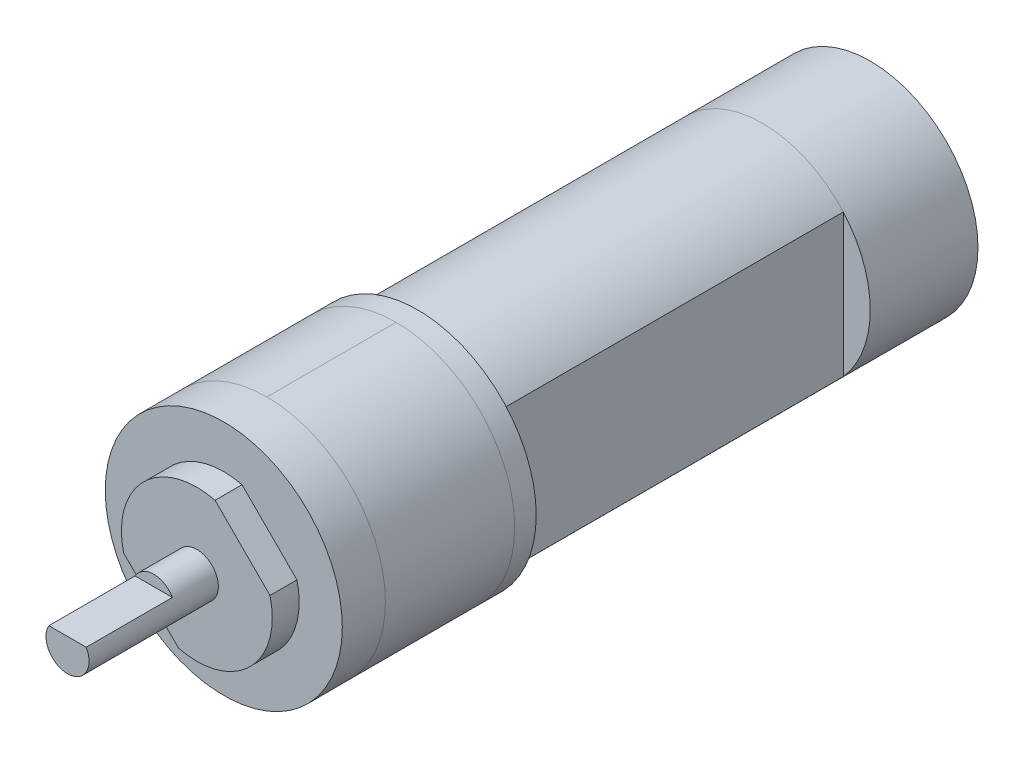
SolidWorks part; units mm, degrees
ref_plane "Front Plane" through (0, 0, 0) normal (0, 0, 1) x (1, 0, 0)
ref_plane "Top Plane" through (0, 0, 0) normal (0, 1, 0) x (1, 0, 0)
ref_plane "Right Plane" through (0, 0, 0) normal (1, 0, 0) x (0, 0, -1)
sketch "Sketch2" plane through (0, 0, 0) normal (1, 0, 0) x (0, 0, -1)
  line L0 (0, 0) -> (0, 11)
  line L1 (0, 11) -> (-18, 11)
  line L2 (-18, 11) -> (-18, 0)
  line L3 (-18, 7) -> (-20.5, 7)
  line L4 (-20.5, 7) -> (-20.5, 0)
  line L5 (-51.2955, 0) -> (51.2955, 0) construction
  line L6 (0, 10) -> (32, 10)
  line L7 (32, 10) -> (32, 0)
  line L8 (32, 10) -> (42, 10)
  line L9 (42, 10) -> (42, 0)
  point P11 (0, 0)
  dimension "D1" = 14
  dimension "D2" = 22
  dimension "D3" = 2.5
  dimension "D4" = 18
  dimension "D5" = 32
  dimension "D6" = 20
  dimension "D7" = 10
revolve "Revolve1" add sketch "Sketch2" angle 360 about L5 region at (0, 5.5, 9) region at (0, 5, -16) region at (0, 3.5, 19.25) region at (0, 5, -37)
sketch "Sketch4" plane through (0, 0, 0) normal (0, 0, -1) x (-1, 0, 0)
  line L1 (-7.5, -11) -> (7.5, -11) construction
  line L2 (-7.5, -11) -> (-7.5, 11) construction
  line L3 (-7.5, 11) -> (7.5, 11) construction
  line L4 (7.5, -11) -> (7.5, 11) construction
  line L5 (-7.5, -11) -> (7.5, 11) construction
  line L6 (-7.5, 11) -> (7.5, -11) construction
  line L7 (-7.5, 11) -> (-11, 11)
  line L8 (-7.5, 11) -> (-7.5, -11)
  line L9 (-7.5, -11) -> (-11, -11)
  line L10 (-11, 11) -> (-11, -11)
  line L11 (7.5, 11) -> (11, 11)
  line L12 (7.5, 11) -> (7.5, -11)
  line L13 (7.5, -11) -> (11, -11)
  line L14 (11, 11) -> (11, -11)
  circle A0 centre (0, 0) radius 11 construction
  point P0 (0, 0)
  dimension "D1" = 15
extrude "Cut-Extrude1" cut sketch "Sketch4" along normal offset from surface (32 mm away) 10 up to face at (10, 0, -42)
sketch "Sketch5" plane through (0, 0, 20.5) normal (0, 0, 1) x (1, 0, 0)
  line L0 (-4.9497, 4.9497) -> (4.9497, -4.9497) construction
  line L1 (0, 0) -> (0, 7) construction
  line L2 (-9.1924, 0.7071) -> (0.7071, -9.1924)
  line L3 (-0.7071, 9.1924) -> (9.1924, -0.7071)
  line L4 (-0.7071, 9.1924) -> (2.8284, 12.7279)
  line L5 (2.8284, 12.7279) -> (12.7279, 2.8284)
  line L6 (12.7279, 2.8284) -> (9.1924, -0.7071)
  line L7 (-9.1924, 0.7071) -> (-12.7279, -2.8284)
  line L8 (-12.7279, -2.8284) -> (-2.8284, -12.7279)
  line L9 (-2.8284, -12.7279) -> (0.7071, -9.1924)
  circle A0 centre (0, 0) radius 7 construction
  circle A1 centre (0, 0) radius 7 construction
  circle A2 centre (0, 0) radius 11 construction
  point P6 (0, 0)
  dimension "D1" = 45
  dimension "D2" = 6
  dimension "D3" = 6
extrude "Cut-Extrude2" cut sketch "Sketch5" against normal up to surface (2.5 mm away) up to face at (7, 0, 18)
sketch "Sketch6" plane through (0, 0, 20.5) normal (0, 0, 1) x (1, 0, 0)
  circle A0 centre (0, 0) radius 2
  dimension "D1" = 4
extrude "Boss-Extrude1" add sketch "Sketch6" along normal blind 12
sketch "Sketch7" plane through (0, 0, 32.5) normal (0, 0, 1) x (1, 0, 0)
  line L1 (-2, 1) -> (2, 1)
  line L2 (-2, 1) -> (-2, 3)
  line L3 (-2, 3) -> (2, 3)
  line L4 (2, 1) -> (2, 3)
  line L5 (-2, 1) -> (2, 3) construction
  line L6 (-2, 3) -> (2, 1) construction
  circle A0 centre (0, 0) radius 2 construction
  circle A1 centre (0, 0) radius 2 construction
  point P0 (0, 2)
  dimension "D1" = 3
extrude "Cut-Extrude3" cut sketch "Sketch7" against normal blind 8
sketch "Sketch8" plane through (0, 0, 0) normal (1, 0, 0) x (0, 0, -1)
  line L0 (0, 11) -> (-18, 11) construction
  line L1 (-14, 11) -> (-2, 11)
  line L2 (-14, 11) -> (-14, -11)
  line L3 (-14, -11) -> (-2, -11)
  line L4 (-2, 11) -> (-2, -11)
  line L5 (-18, -11) -> (0, -11) construction
  line L6 (32, 10) -> (32, -10)
  line L7 (42, 10) -> (0, 10) construction
  line L8 (0, -10) -> (42, -10) construction
  line L9 (32, -6.6144) -> (32, 6.6144) construction
  line L10 (-18, 11) -> (-18, -11) construction
  line L11 (0, -6.6144) -> (0, 6.6144) construction
  point P14 (27.629, -10)
  dimension "D1" = 4
  dimension "D2" = 2
split line "Split Line1"
